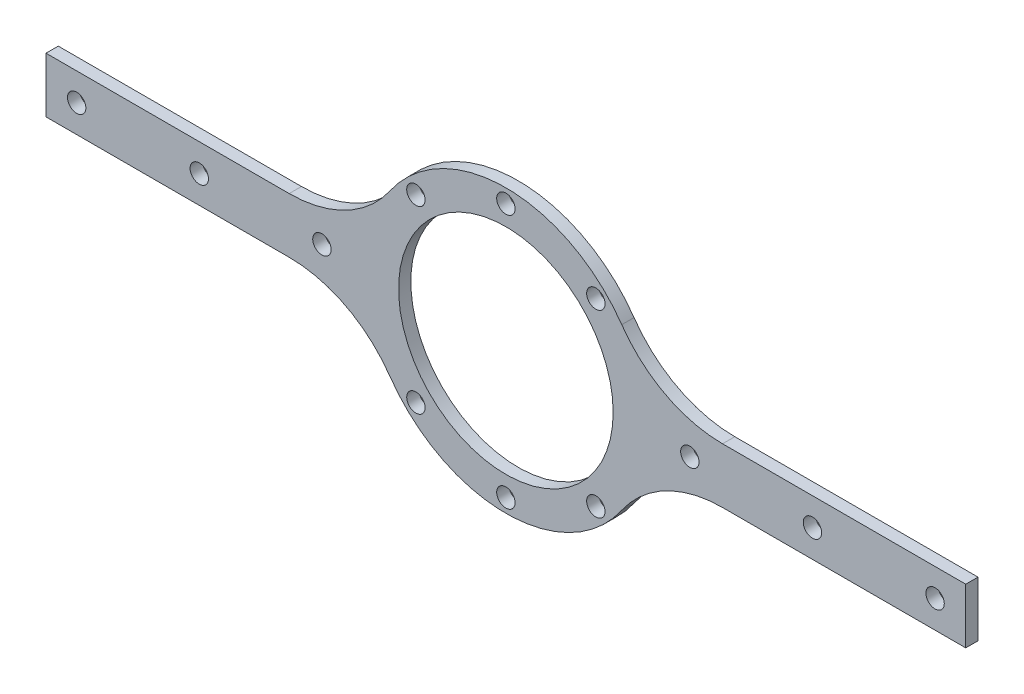
SolidWorks part; units mm, degrees
ref_plane "前视基准面" through (0, 0, 0) normal (0, 0, 1) x (1, 0, 0)
ref_plane "上视基准面" through (0, 0, 0) normal (0, 1, 0) x (1, 0, 0)
ref_plane "右视基准面" through (0, 0, 0) normal (1, 0, 0) x (0, 0, -1)
other "Configuration Table"
sketch "草图1" plane through (0, 0, 0) normal (0, 0, 1) x (1, 0, 0)
  line L0 (22.5555, 4.5) -> (75, 4.5)
  line L1 (-75, -4.5) -> (-22.5555, -4.5)
  line L2 (-75, -4.5) -> (-75, 4.5)
  line L3 (-75, 4.5) -> (-22.5555, 4.5)
  line L4 (75, -4.5) -> (75, 4.5)
  line L5 (-75, -4.5) -> (75, 4.5) construction
  line L6 (-75, 4.5) -> (75, -4.5) construction
  line L7 (22.5555, -4.5) -> (75, -4.5)
  line L8 (-70, 0) -> (-75, 0) construction
  circle A0 centre (0, 20.75) radius 1.5
  circle A1 centre (14.6725, 14.6725) radius 1.5
  circle A2 centre (20.75, 0) radius 1.5 construction
  circle A3 centre (14.6725, -14.6725) radius 1.5
  circle A4 centre (0, -20.75) radius 1.5
  circle A5 centre (-14.6725, -14.6725) radius 1.5
  circle A6 centre (-20.75, 0) radius 1.5 construction
  circle A7 centre (-14.6725, 14.6725) radius 1.5
  circle A8 centre (0, 0) radius 17.5
  circle A9 centre (0, 0) radius 23 construction
  arc A10 (-22.5555, 4.5) -> (22.5555, 4.5) centre (0, 0) cw
  arc A11 (22.5555, -4.5) -> (-22.5555, -4.5) centre (0, 0) cw
  circle A12 centre (-70, 0) radius 1.5
  circle A13 centre (-50, 0) radius 1.5
  circle A14 centre (-30, 0) radius 1.5
  circle A15 centre (-10, 0) radius 1.5 construction
  circle A17 centre (30, 0) radius 1.5
  circle A18 centre (50, 0) radius 1.5
  circle A19 centre (70, 0) radius 1.5
  circle A21 centre (10, 0) radius 1.5
  circle A22 centre (90, 0) radius 1.5
  point P19 (0, 0)
  point P25 (22.5555, 4.5)
  point P26 (22.5555, -4.5)
  point P27 (-22.5555, 4.5)
  point P28 (-22.5555, -4.5)
  dimension "D2" = 3
  dimension "D4" = 35
  dimension "D5" = 46
  dimension "D8" = 3
  dimension "D1" = 20.75
  dimension "D3" = 8
  dimension "D6" = 9
  dimension "D7" = 150
  dimension "D9" = 5
  dimension "D11" = 20
  dimension "D10" = 9
base flange "基体-法兰1" sketch "草图1" thickness 2 reverse thickness direction no parameters "D1"=0.7366
fillet "圆角1" radius 20 4 edges at (22.5555, -4.5, -1) (22.5555, 4.5, -1) (-22.5555, -4.5, -1) (-22.5555, 4.5, -1)
sketch "折弯-线1" plane through (0, 0, 0) normal (0, 1, 0) x (1, 0, 0)
sketch "边界框1" plane through (0, 0, 0) normal (0, 1, 0) x (1, 0, 0)
sheet metal parameters "钣金6" thickness 2 parameters "D1"=0.7366
flat pattern "平板型式6" [suppressed]
sketch "折弯-线2" plane through (0, 0, 0) normal (0, 1, 0) x (1, 0, 0)
sketch "边界框2" [suppressed] plane through (0, 0, 0) normal (0, 1, 0) x (1, 0, 0)
